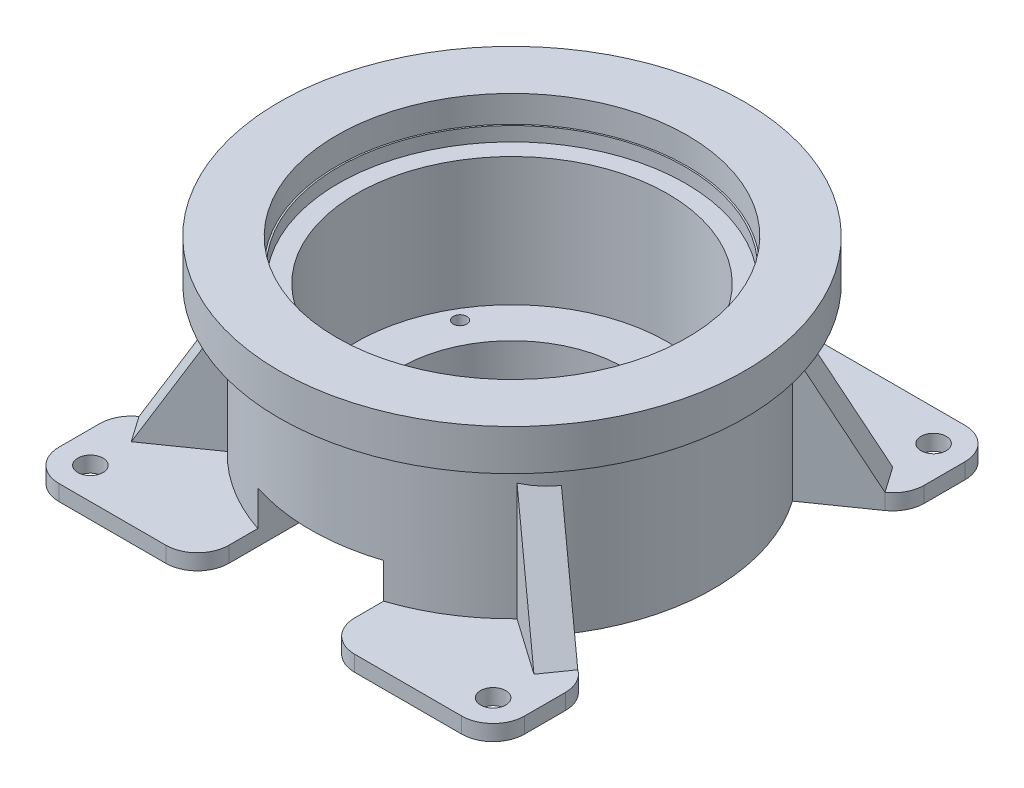
SolidWorks part; units mm, degrees
ref_plane "前视基准面" through (0, 0, 0) normal (0, 0, 1) x (1, 0, 0)
ref_plane "上视基准面" through (0, 0, 0) normal (0, 1, 0) x (1, 0, 0)
ref_plane "右视基准面" through (0, 0, 0) normal (1, 0, 0) x (0, 0, -1)
sketch "草图1" plane through (0, 0, 0) normal (0, 1, 0) x (1, 0, 0)
  circle A0 centre (0, 0) radius 64
  circle A1 centre (0, 0) radius 49
extrude "凸台-拉伸1" add sketch "草图1" along normal blind 52
sketch "草图13" plane through (0, 0, 0) normal (0, -1, 0) x (1, 0, 0)
  circle A0 centre (0, 0) radius 49
  circle A1 centre (0, 0) radius 35.5
extrude "凸台-拉伸3" add sketch "草图13" against normal blind 11.2
sketch "草图16" plane through (0, 0, 0) normal (0, -1, 0) x (1, 0, 0)
  line L4 (38.9709, -21.4104) -> (38.9709, -22.5004) construction
  line L6 (38.9709, -22.5004) -> (0, 0) construction
  line L7 (0, 0) -> (-38.9709, 22.5004) construction
  line L12 (38.3313, 33.5681) -> (38.3313, 23.5735) construction
  line L14 (38.3313, 23.5735) -> (38.3313, 22.4835) construction
  line L18 (38.3313, 22.4835) -> (39.1744, 22.4835) construction
  line L20 (38.978, 22.4835) -> (0, 0) construction
  line L21 (0, 0) -> (-38.98, -22.4846) construction
  arc A0 (-1.2467, 44.9827) -> (38.9709, -22.5004) centre (0, 0) cw construction
  arc A1 (-1.2467, 44.9827) -> (-38.9709, 22.5004) centre (0, 0) ccw construction
  arc A2 (-38.98, -22.4846) -> (-38.9709, 22.5004) centre (0, 0) cw construction
  point P25 (38.9709, -22.5004)
  point P41 (-38.9709, 22.5004)
  point P103 (38.978, 22.4835)
  point P128 (-38.98, -22.4846)
hole_wizard "M4 六角圆柱头螺钉的柱形沉头孔11" positions "草图16" profile "草图17" counterbore size "M4" standard "GB" end condition up to next
sketch "草图17" plane through (-38.98, 0, -22.4846) normal (1, 0, 0) x (0, 0, -1)
  line L0 (0, 0) -> (0, 11.2)
  line L1 (0, 11.2) -> (2.15, 11.2)
  line L3 (2.15, 11.2) -> (2.15, 5.2)
  line L4 (2.15, 5.2) -> (3.55, 5.2)
  line L5 (3.55, 5.2) -> (3.55, 0)
  line L7 (3.55, 0) -> (0, 0)
  line L11 (0, -6.35) -> (0, 107.95) construction
  dimension "通孔孔直径" = 4.3
  dimension "通孔孔深度" = 11.2
  dimension "柱形沉头孔直径" = 7.1
  dimension "柱形沉头孔深度" = 5.2
sketch "草图18" plane through (0, 52, 0) normal (0, 1, 0) x (1, 0, 0)
  circle A0 centre (0, 0) radius 74
  circle A1 centre (0, 0) radius 56
extrude "凸台-拉伸4" add sketch "草图18" along normal blind 13
sketch "草图25" plane through (0, 0, 0) normal (0, -1, 0) x (1, 0, 0)
  line L0 (-74, 57.021) -> (-74, 70)
  line L1 (-64, 80) -> (64, 80)
  line L2 (74, 70) -> (74, 57.021)
  line L3 (-52.4257, 36.7089) -> (-69.7358, 48.8295)
  line L4 (52.4257, 36.7089) -> (69.7358, 48.8295)
  arc A1 (-74, 70) -> (-64, 80) centre (-64, 70) cw
  arc A2 (74, 70) -> (64, 80) centre (64, 70) ccw
  arc A3 (-74, 57.021) -> (-69.7358, 48.8295) centre (-64, 57.021) ccw
  arc A4 (74, 57.021) -> (69.7358, 48.8295) centre (64, 57.021) cw
  arc A5 (-52.4257, 36.7089) -> (52.4257, 36.7089) centre (0, 0) cw
  circle A6 centre (0, 0) radius 64 construction
  circle A7 centre (-64, 70) radius 4
  circle A8 centre (64, 70) radius 4
  point P8 (-74, 80)
  point P11 (74, 80)
  dimension "D3" = 10
  dimension "D4" = 10
  dimension "D1" = 10
  dimension "D2" = 10
extrude "凸台-拉伸7" add sketch "草图25" against normal blind 5
sketch "草图28" plane through (0, 0, 0) normal (0, -1, 0) x (1, 0, 0)
  line L0 (-52.4257, -36.7089) -> (-69.7358, -48.8295)
  line L2 (-74, -57.021) -> (-74, -70)
  line L3 (-64, -80) -> (64, -80)
  line L4 (74, -57.021) -> (74, -70)
  line L5 (43.4587, -46.9824) -> (74, -80) construction
  line L6 (-74, -80) -> (-43.4587, -46.9824) construction
  line L7 (52.4257, -36.7089) -> (69.7358, -48.8295)
  arc A0 (-64, -80) -> (-74, -70) centre (-64, -70) cw
  arc A1 (74, -70) -> (64, -80) centre (64, -70) cw
  arc A2 (-52.4257, -36.7089) -> (52.4257, -36.7089) centre (0, 0) ccw
  circle A3 centre (0, 0) radius 64 construction
  arc A4 (-74, -57.021) -> (-69.7358, -48.8295) centre (-64, -57.021) cw
  arc A5 (74, -57.021) -> (69.7358, -48.8295) centre (64, -57.021) ccw
  circle A6 centre (-64, -70) radius 4
  circle A7 centre (64, -70) radius 4
  point P0 (0, 0)
  dimension "D3" = 10
  dimension "D4" = 10
  dimension "D1" = 10
  dimension "D5" = 10
  dimension "D2" = 148
extrude "凸台-拉伸8" add sketch "草图28" against normal blind 5
sketch "草图14" plane through (0, 0, 0) normal (0, 0, 1) x (1, 0, 0)
  line L0 (0, 0) -> (20, 0)
  line L1 (-64, 0) -> (64, 0) construction
  line L2 (20, 0) -> (20, 16.2)
  line L3 (20, 16.2) -> (-20, 16.2)
  line L4 (-20, 16.2) -> (-20, 0)
  line L5 (-20, 0) -> (0, 0)
  dimension "D1" = 20
  dimension "D2" = 16.2
  dimension "D4" = 20
extrude "切除-拉伸2" cut sketch "草图14" along normal blind 81
fillet "圆角4" radius 10 1 edges at (-20, 2.5, 80) type face fillet first side face at (-20, 8.1, 53.7143) second side face at (-42, 2.5, 80)
fillet "圆角5" radius 10 1 edges at (20, 2.5, 80) type face fillet first side face at (20, 8.1, 53.7143) second side face at (42, 2.5, 80)
sketch "草图32" plane through (0, 0, 0) normal (0.5736, 0, -0.8192) x (-0.8192, 0, -0.5736)
  line L0 (-64, 41) -> (-64, 5) construction
  line L1 (-64, 52) -> (-64, 5) construction
  line L2 (-85.1316, 5) -> (-64, 41)
rib "筋1" sketch "草图32" sketch "草图32" thickness 10 extrusion direction parallel to sketch draft on no parameters "D1"=10
sketch "草图33" plane through (0, 0, 0) normal (-0.5736, 0, -0.8192) x (-0.8192, 0, 0.5736)
  line L0 (64, 5) -> (64, 41) construction
  line L1 (64, 5) -> (64, 52) construction
  line L2 (64, 41) -> (85.1316, 5)
rib "筋2" sketch "草图33" sketch "草图33" thickness 10 extrusion direction parallel to sketch draft on no parameters "D1"=10
sketch "草图34" plane through (0, 0, 0) normal (-0.5736, 0, 0.8192) x (0.8192, 0, 0.5736)
  line L0 (-64, 5) -> (-64, 41) construction
  line L1 (-64, 52) -> (-64, 5) construction
  line L2 (-85.1316, 5) -> (-64, 41)
rib "筋7" sketch "草图34" sketch "草图34" thickness 10 extrusion direction parallel to sketch draft on no parameters "D1"=10
sketch "草图35" plane through (0, 0, 0) normal (0.5736, 0, 0.8192) x (0.8192, 0, -0.5736)
  line L0 (64, 5) -> (64, 41) construction
  line L1 (64, 5) -> (64, 52) construction
  line L2 (64, 41) -> (85.1316, 5)
rib "筋9" sketch "草图35" sketch "草图35" thickness 10 extrusion direction parallel to sketch draft on no parameters "D1"=10
sketch "草图36" plane through (0, 52, 0) normal (0, 1, 0) x (1, 0, 0)
  circle A0 centre (0, 0) radius 56
  circle A1 centre (0, 0) radius 55
extrude "凸台-拉伸9" add sketch "草图36" along normal up to surface (13 mm away) up to face at (0, 65, 56)
sketch "草图37" plane through (0, 65, 0) normal (0, 1, 0) x (1, 0, 0)
  circle A0 centre (0, 0) radius 55.5
extrude "切除-拉伸3" cut sketch "草图37" against normal blind 8.5
sketch "草图38" plane through (0, 0, 0) normal (0, 1, 0) x (1, 0, 0)
  circle A0 centre (0, 0) radius 49.5
extrude "切除-拉伸4" cut sketch "草图38" against normal up to surface (-11.2 mm away) from surface up to face at (0, 11.2, -2.6094) starting at face at (0, 52, 49)
sketch "草图39" plane through (0, 0, 0) normal (0, 1, 0) x (1, 0, 0)
  circle A0 centre (0, 0) radius 55.2
extrude "切除-拉伸5" cut sketch "草图39" along normal up to surface (56.5 mm away) from surface up to face at (0, 56.5, 55) starting at face at (0, 52, 49.5)
sketch "草图40" plane through (0, 0, 0) normal (0, 1, 0) x (1, 0, 0)
  circle A0 centre (0, 0) radius 55.7
extrude "切除-拉伸6" cut sketch "草图40" against normal up to surface (-56.5 mm away) from surface up to face at (0, 56.5, 55.2) starting at face at (0, 65, 55.5)
